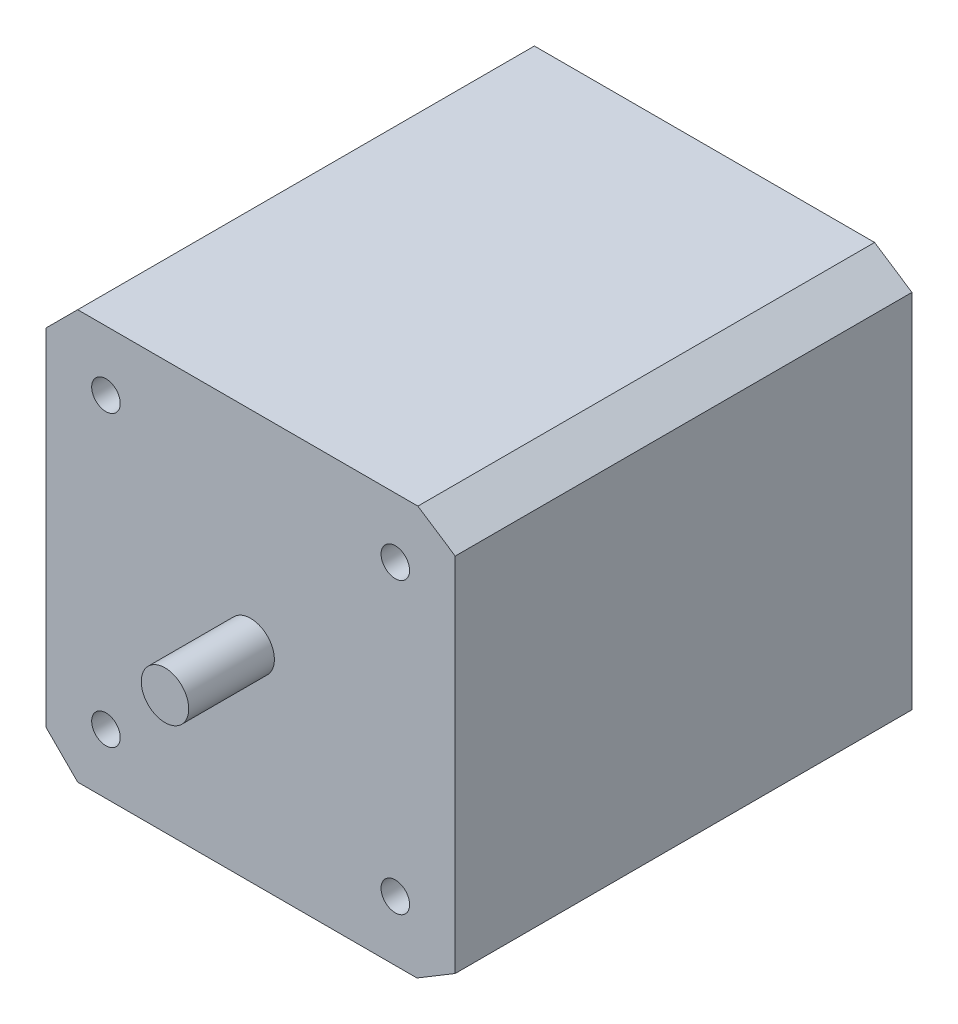
SolidWorks part; units mm, degrees
ref_plane "Front Plane" through (0, 0, 0) normal (0, 0, 1) x (1, 0, 0)
ref_plane "Top Plane" through (0, 0, 0) normal (0, 1, 0) x (1, 0, 0)
ref_plane "Right Plane" through (0, 0, 0) normal (1, 0, 0) x (0, 0, -1)
sketch "Sketch1" plane through (0, 0, 0) normal (0, 0, 1) x (1, 0, 0)
  line L0 (-18.5054, 18.1792) -> (-15.1847, 21.5)
  line L1 (-18.5054, 21.5) -> (24.4946, 21.5)
  line L2 (-18.5054, 21.5) -> (-18.5054, -21.5)
  line L3 (-18.5054, -21.5) -> (24.4946, -21.5)
  line L4 (24.4946, 21.5) -> (24.4946, -21.5)
  line L5 (-18.5054, 21.5) -> (24.4946, -21.5) construction
  line L6 (-18.5054, -21.5) -> (24.4946, 21.5) construction
  line L7 (20.5734, 21.5) -> (24.4946, 18.9156)
  line L8 (-18.5054, -18.1792) -> (-15.1847, -21.5)
  line L9 (20.4702, -21.5) -> (24.4946, -19.0795)
  line L11 (-18.5054, 8.0376) -> (-23.9363, 8.0376)
  line L12 (-18.5054, 8.0376) -> (-18.5054, -7.9631)
  line L13 (-18.5054, -7.9631) -> (-23.9363, -7.9631)
  line L14 (-23.9363, 8.0376) -> (-23.9363, -7.9631)
  line L15 (-18.5054, 8.0376) -> (-23.9363, -7.9631) construction
  line L16 (-18.5054, -7.9631) -> (-23.9363, 8.0376) construction
  circle A0 centre (2.9946, 0) radius 2.4955
  circle A1 centre (2.9946, 0) radius 11.5
  circle A2 centre (-12.2112, 15.2058) radius 1.5
  circle A3 centre (18.2004, 15.2058) radius 1.5
  circle A4 centre (18.2004, -15.2058) radius 1.5
  circle A5 centre (-12.2112, -15.2058) radius 1.5
  point P4 (2.9946, 0)
  point P28 (-21.2209, 0.0372)
  dimension "D2" = 23
  dimension "D3" = 3
  dimension "D1" = 43
  dimension "D4" = 45
extrude "Boss-Extrude1" add sketch "Sketch1" along normal blind 48 contours L3 L9 L4 L7 L1 L0 L2 L8 A5 A4 A3 A2 A1 | A1 A0 | A0 region at (-16.415, 19.4096, 0) region at (2.9946, 0, 0) region at (-8.1801, 0, 0)
extrude "Boss-Extrude2" add sketch "Sketch1<3>" along normal blind 35 contours A1
sketch "Sketch1<3>" plane through (0, 0, 0) normal (0, 0, 1) x (1, 0, 0) same geometry as "Sketch1"
extrude "Boss-Extrude3" add sketch "Sketch1<4>" along normal blind 57 contours A0
sketch "Sketch1<4>" plane through (0, 0, 0) normal (0, 0, 1) x (1, 0, 0) same geometry as "Sketch1"
extrude "Boss-Extrude4" add sketch "Sketch1<5>" along normal blind 7 contours L13 L14 L11 L12
sketch "Sketch1<5>" plane through (0, 0, 0) normal (0, 0, 1) x (1, 0, 0) same geometry as "Sketch1"
